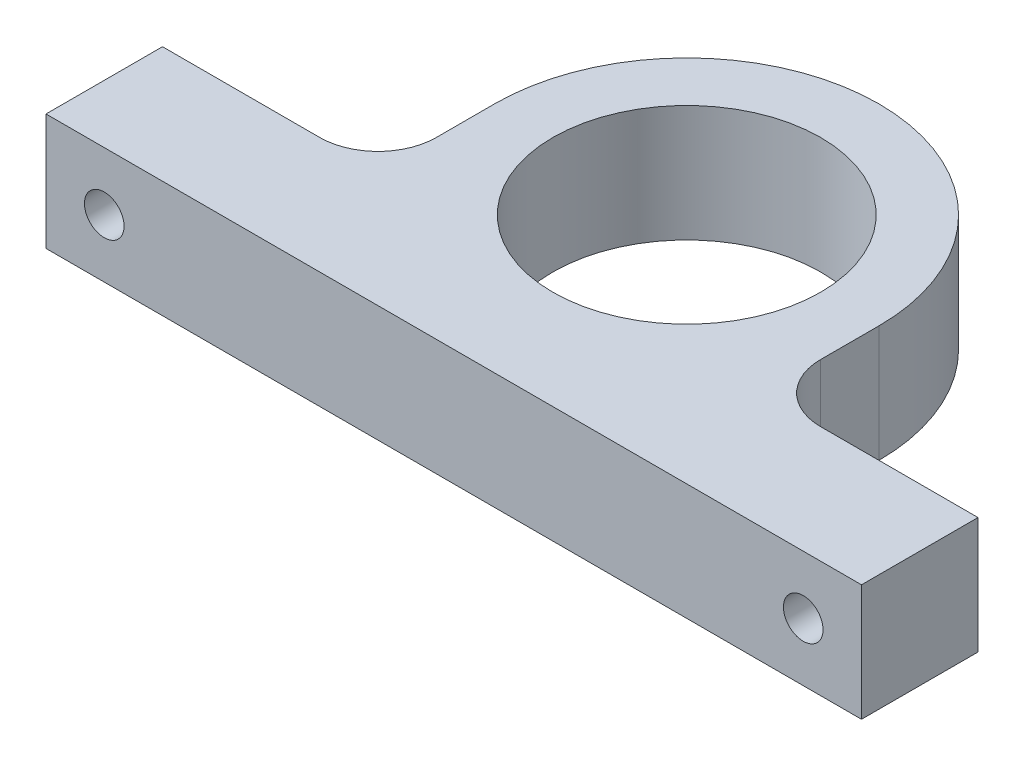
SolidWorks part; units mm, degrees
ref_plane "Front Plane" through (0, 0, 0) normal (0, 0, 1) x (1, 0, 0)
ref_plane "Top Plane" through (0, 0, 0) normal (0, 1, 0) x (1, 0, 0)
ref_plane "Right Plane" through (0, 0, 0) normal (1, 0, 0) x (0, 0, -1)
sketch "Sketch1" plane through (0, 0, 0) normal (0, 1, 0) x (1, 0, 0)
  line L0 (0, 0) -> (0, 20) construction
  line L5 (35, 0) -> (-35, 0)
  line L6 (-35, 0) -> (-35, 10)
  line L7 (-16.5, 10) -> (-35, 10)
  line L8 (-16.5, 20) -> (-16.5, 10)
  line L9 (0, 20) -> (0, 120.2965) construction
  line L10 (16.5, 20) -> (16.5, 10)
  line L11 (16.5, 10) -> (35, 10)
  line L12 (35, 0) -> (35, 10)
  circle A0 centre (0, 20) radius 11.5
  arc A1 (16.5, 20) -> (-16.5, 20) centre (0, 20) ccw
  dimension "D1" = 23
  dimension "D2" = 35
  dimension "D4" = 5
  dimension "D3" = 10
  dimension "D5" = 10
extrude "Boss-Extrude1" add sketch "Sketch1" along normal blind 10
fillet "Fillet1" radius 5 2 edges at (-16.5, 5, -10) (16.5, 5, -10)
sketch "Sketch2" plane through (0, 0, -10) normal (0, 0, -1) x (-1, 0, 0)
  line L0 (0, 0) -> (0, 10) construction
  line L1 (-16.5, 0) -> (16.5, 0) construction
  line L2 (16.5, 10) -> (-16.5, 10) construction
  line L3 (-35, 10) -> (-21.5, 10) construction
  line L4 (-35, 10) -> (-35, 0) construction
  point P0 (-30, 5)
  point P8 (30, 5)
  dimension "D1" = 5
  dimension "D2" = 5
hole_wizard "CSK for M3 Flat Head Machine Screw1" positions "3DSketch1" profile "Sketch3" countersink size "M3" standard "ANSI Metric" end condition through all
sketch3d "3DSketch1"
  point P0 (30, 5, -10)
  point P3 (-30, 5, -10)
sketch "Sketch3" plane through (30, 5, -10) normal (1, 0, 0) x (0, 1, 0)
  line L0 (0, 0) -> (0, 10)
  line L1 (0, 10) -> (1.7, 10)
  line L2 (1.7, 10) -> (1.7, 1.45)
  line L3 (1.7, 1.45) -> (3.15, 0)
  line L5 (3.15, 0) -> (0, 0)
  line L6 (-1.7, 1.45) -> (-3.15, 0) construction
  line L11 (0, -6.35) -> (0, 107.95) construction
  dimension "Thru Hole Dia." = 3.4
  dimension "Thru Hole Depth" = 10
  dimension "Near C'Sink Dia." = 6.3
  dimension "Near C'Sink Angle" = 90
